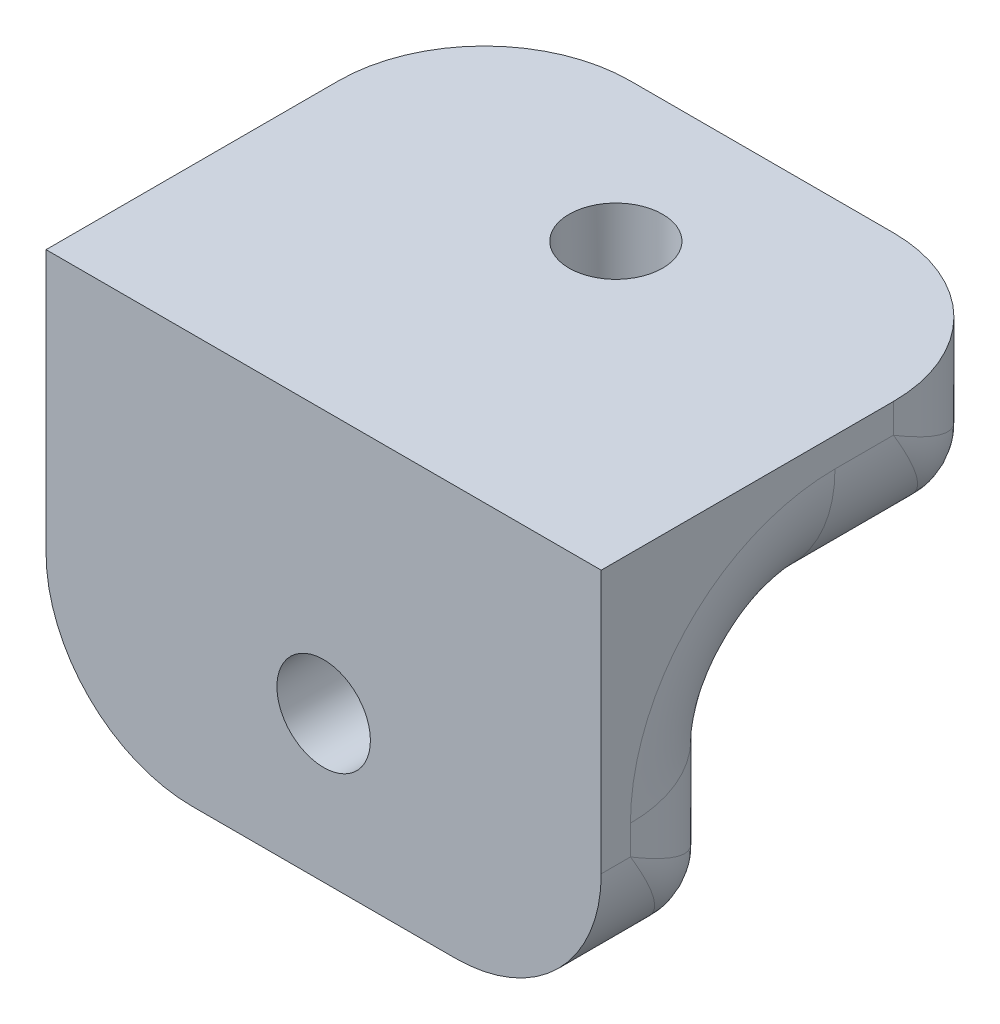
SolidWorks part; units mm, degrees
material "ABS"
ref_plane "Front" through (0, 0, 0) normal (0, 0, 1) x (1, 0, 0)
ref_plane "Top" through (0, 0, 0) normal (0, 1, 0) x (1, 0, 0)
ref_plane "Right" through (0, 0, 0) normal (1, 0, 0) x (0, 0, -1)
sketch "Esquisse1" plane through (0, 0, 0) normal (1, 0, 0) x (0, 0, -1)
  line L0 (15, 0) -> (0, 0)
  line L1 (0, 0) -> (0, -14)
  dimension "D1" = 90
  dimension "D2" = 15
  dimension "D3" = 14
extrude "Extru.-Mince1" add sketch "Esquisse1" along normal mid plane 19 thin thin type one direction reverse wall 6
fillet "Congé2" radius 2 3 edges at (0, -14, -6) (0, -6, -15) (0, -6, -6)
sketch "Esquisse2" plane through (0, 0, 0) normal (0, 1, 0) x (1, 0, 0)
  line L3 (9.5, 0) -> (-9.5, 0) construction
  line L4 (9.5, 15) -> (-9.5, 15) construction
  circle A1 centre (0, 10) radius 1.6
  dimension "D1" = 10
  dimension "D2" = 5
  dimension "D3" = 3.2
extrude "Enlèv. mat.-Extru.1" cut sketch "Esquisse2" against normal through all
sketch "Esquisse3" plane through (0, 0, 0) normal (0, 0, 1) x (1, 0, 0)
  line L0 (9.5, -14) -> (-9.5, -14) construction
  line L2 (9.5, 0) -> (-9.5, 0) construction
  circle A0 centre (0, -9) radius 1.6
  dimension "D1" = 5
  dimension "D2" = 3.2
  dimension "D3" = 9
extrude "Enlèv. mat.-Extru.2" cut sketch "Esquisse3" against normal through all
sketch "Esquisse4" plane through (0, 0, 0) normal (0, 1, 0) x (1, 0, 0)
  circle A0 centre (0, 10) radius 3
  circle A1 centre (0, 10) radius 1.6 construction
  dimension "D1" = 6
extrude "Enlèv. mat.-Extru.3" cut sketch "Esquisse4" against normal through all from offset 2.5 offset against normal yes
sketch "Esquisse5" plane through (0, 0, 0) normal (0, 0, 1) x (1, 0, 0)
  line L13 (-1.5877, -6.25) -> (-3.1754, -9)
  line L14 (-3.1754, -9) -> (-1.5877, -11.75)
  line L15 (-1.5877, -11.75) -> (1.5877, -11.75)
  line L16 (1.5877, -11.75) -> (3.1754, -9)
  line L17 (3.1754, -9) -> (1.5877, -6.25)
  line L18 (1.5877, -6.25) -> (-1.5877, -6.25)
  circle A3 centre (0, -9) radius 2.75 construction
  dimension "D1" = 5.5
extrude "Enlèv. mat.-Extru.4" cut sketch "Esquisse5" against normal blind 8 from offset 3 offset against normal yes
fillet "Congé1" radius 5 14 edges at (9.5, -2, -15) (-9.5, -2, -15) (9.5, -14, -2) (9.5, -13.4142, -5.4142) (9.5, -10, -6) (9.5, -6.5858, -6.5858) (9.5, -6, -10.5) (9.5, -5.4142, -14.4142) (-9.5, -14, -2) (-9.5, -13.4142, -5.4142) (-9.5, -10, -6) (-9.5, -6.5858, -6.5858) (-9.5, -6, -10.5) (-9.5, -5.4142, -14.4142)
sketch "Esquisse6" plane through (0, 0, 0) normal (0, 1, 0) x (1, 0, 0)
  line L0 (4.5, 15) -> (-4.5, 15) construction
  line L1 (-2.35, 15) -> (2.35, 15)
  line L2 (-2.35, 15) -> (-2.35, 0)
  line L3 (-2.35, 0) -> (2.35, 0)
  line L4 (2.35, 15) -> (2.35, 0)
  circle A0 centre (0, 10) radius 1.6 construction
  circle A1 centre (0, 10) radius 1.6
  dimension "D1" = 4.7
extrude "Boss.-Extru.1" [suppressed] add sketch "Esquisse6" along normal blind 1.5
fillet "Congé3" [suppressed] radius 0.5
sketch "Esquisse7" plane through (0, 0, 0) normal (0, 0, 1) x (1, 0, 0)
  circle A1 centre (0, -9) radius 1.6 construction
  circle A2 centre (0, -9) radius 1.6
extrude "Boss.-Extru.2" [suppressed] add sketch "Esquisse7" against normal blind 0.2
sketch "Sketch1" [suppressed] plane through (0, 0, -15) normal (0, 0, -1) x (-1, 0, 0)
  line L1 (-2.35, 0) -> (3.0183, 0)
  line L2 (-2.35, 0) -> (-2.35, 3.1233)
  line L3 (-2.35, 3.1233) -> (3.0183, 3.1233)
  line L4 (3.0183, 0) -> (3.0183, 3.1233)
extrude "Cut-Extrude1" [suppressed] cut sketch "Sketch1" against normal through all
